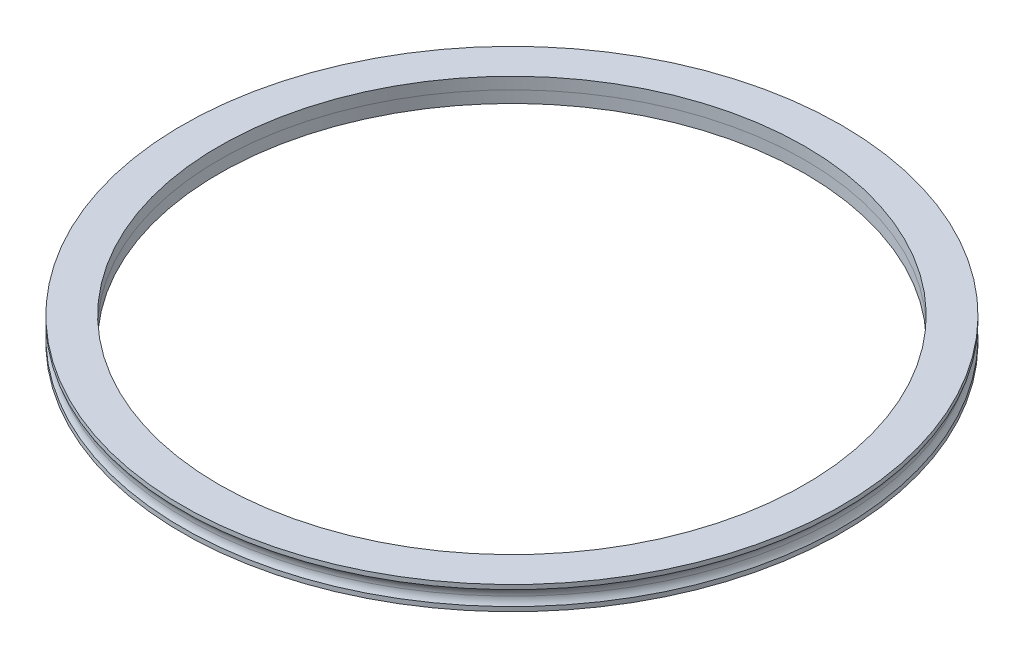
SolidWorks part; units mm, degrees
material "AISI 4340 Steel, normalized"
ref_plane "Front Plane" through (0, 0, 0) normal (0, 0, 1) x (1, 0, 0)
ref_plane "Top Plane" through (0, 0, 0) normal (0, 1, 0) x (1, 0, 0)
ref_plane "Right Plane" through (0, 0, 0) normal (1, 0, 0) x (0, 0, -1)
sketch "Sketch1" plane through (0, 0, 0) normal (0, 0, 1) x (1, 0, 0)
  line L0 (-67.5, 17.585) -> (-67.5, 18.5) construction
  line L1 (-60, 13.67) -> (-60, 18.5) construction
  line L2 (-60, 13.67) -> (-67.5, 13.67) construction
  line L3 (-67.5, 13.67) -> (-67.5, 14.585) construction
  line L4 (-67.5, 17.585) -> (-67.5, 18.5)
  line L5 (-60, 13.67) -> (-60, 18.5)
  line L6 (-60, 13.67) -> (-67.5, 13.67)
  line L7 (-67.5, 13.67) -> (-67.5, 14.585)
  line L8 (-60, 18.5) -> (-67.5, 18.5)
  line L10 (0, -200069.0475) -> (0, 200086.9028) construction
  line L11 (0, -200069.0475) -> (0, 200086.9028) construction
  arc A0 (-67.5, 14.585) -> (-67.5, 17.585) centre (-69.5, 16.085) ccw construction
  arc A1 (-67.5, 14.585) -> (-67.5, 17.585) centre (-69.5, 16.085) ccw
revolve "Revolve1" add sketch "Sketch1" angle 360 about L11
ref_plane "Midplane" through (0, 16.085, 0) normal (0, 1, 0) x (1, 0, 0)
split "Split1" trim tools "Midplane" bodies to split 101 resulting bodies 102 103
